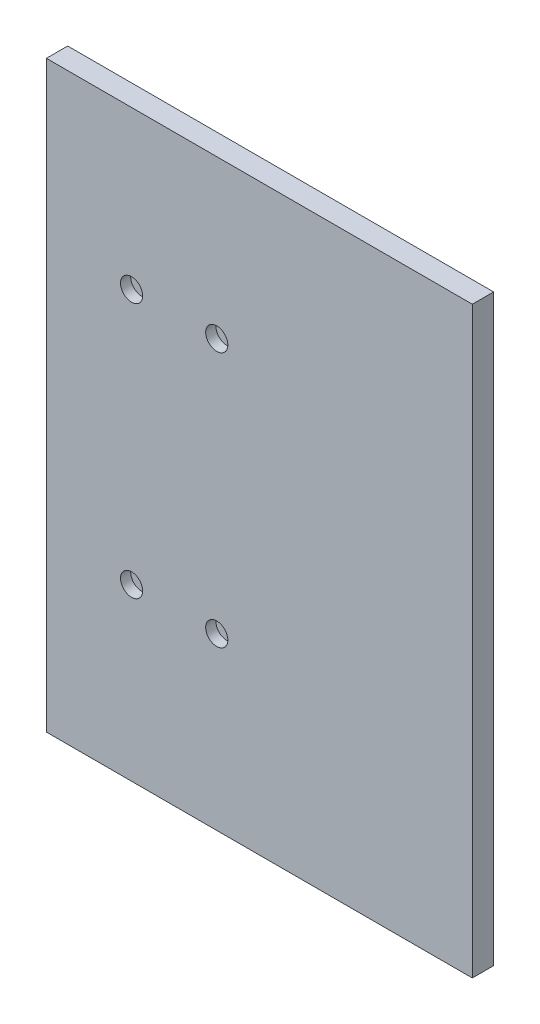
SolidWorks part; units mm, degrees
material "ABS"
ref_plane "Front Plane" through (0, 0, 0) normal (0, 0, 1) x (1, 0, 0)
ref_plane "Top Plane" through (0, 0, 0) normal (0, 1, 0) x (1, 0, 0)
ref_plane "Right Plane" through (0, 0, 0) normal (1, 0, 0) x (0, 0, -1)
sketch "Sketch1" plane through (0, 0, 0) normal (0, 0, 1) x (1, 0, 0)
  line L0 (0, 173.99) -> (63.5, 173.99)
  line L1 (0, 173.99) -> (-63.5, 173.99)
  line L7 (-63.5, 173.99) -> (-63.5, 0)
  line L8 (63.5, 173.99) -> (63.5, 0)
  line L9 (63.5, 0) -> (-63.5, 0)
extrude "Boss-Extrude1" add sketch "Sketch1" along normal blind 6.35
sketch "Sketch2" plane through (0, 0, 0) normal (0, 0, -1) x (-1, 0, 0)
  circle A0 centre (-48.26, 134.62) radius 3.302
  circle A1 centre (-7.62, 134.62) radius 3.302
  circle A2 centre (-48.26, 50.8) radius 3.302
  circle A3 centre (-7.62, 50.8) radius 3.302
sketch "Sketch3" plane through (0, 0, 6.35) normal (0, 0, 1) x (1, 0, 0)
  circle A0 centre (-38.1, 127) radius 3.302
  circle A1 centre (-12.7, 127) radius 3.302
  circle A2 centre (-38.1, 50.8) radius 3.302
  circle A3 centre (-12.7, 50.8) radius 3.302
extrude "Cut-Extrude1" cut sketch "Sketch3" against normal blind 3.048 contours A0 | A1 | A3 | A2
extrude "Cut-Extrude2" cut sketch "Sketch2" against normal blind 3.048 contours A0 | A1 | A3 | A2
